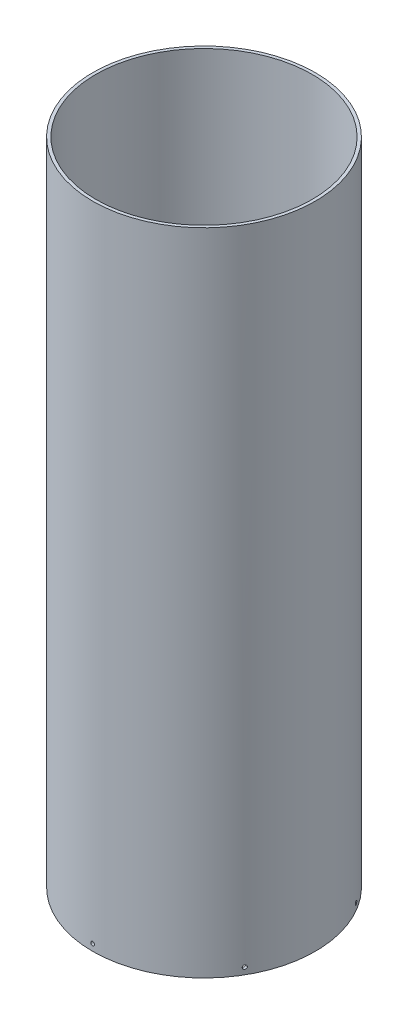
SolidWorks part; units mm, degrees
ref_plane "Front Plane" through (0, 0, 0) normal (0, 0, 1) x (1, 0, 0)
ref_plane "Top Plane" through (0, 0, 0) normal (0, 1, 0) x (1, 0, 0)
ref_plane "Right Plane" through (0, 0, 0) normal (1, 0, 0) x (0, 0, -1)
sketch "Sketch1" plane through (0, 0, 0) normal (0, 1, 0) x (1, 0, 0)
  circle A0 centre (0, 0) radius 76.2
  circle A1 centre (0, 0) radius 78.359
  dimension "D1" = 152.4
  dimension "D2" = 156.718
extrude "Boss-Extrude1" add sketch "Sketch1" along normal blind 457.2
ref_axis "Axis1" through (0, 457.2, 0) along (0, -1, 0)
sketch "Sketch2" plane through (0, 0, 0) normal (0, 0, 1) x (1, 0, 0)
  line L0 (0, 0) -> (0, 4.7625) construction
  circle A0 centre (0, 4.7625) radius 1.3526
  dimension "D1" = 2.7051
  dimension "D2" = 4.7625
extrude "Cut-Extrude1" cut sketch "Sketch2" against normal through all
pattern_circular "CirPattern1" count 6 over 360 about axis through (0, 457.2, 0) along (0, -1, 0) of "Cut-Extrude1"
equation "\"D1@Boss-Extrude1\"=\"Aft_Upper_Length\""
equation "\"AB_Coupling_Section_Length\"= 0.375in"
equation "\"AB_Coupler_Num_Screws\"= 6"
equation "\"AB_Coupling_Screw_Diameter\"= 0.1065in"
equation "\"AB_Coupler_OD_Length\"= 2in"
equation "\"AB_Coupler_Length\"= \"AB_Coupler_OD_Length\" + \"AB_Coupling_Section_Length\" * 2"
equation "\"D1@Sketch2\"=\"AB_Coupling_Screw_Diameter\""
equation "\"D2@Sketch2\"=\"AB_Coupling_Section_Length\"/2"
equation "\"D1@CirPattern1\"=\"AB_Coupler_Num_Screws\""
equation "\"Aft_Section_Length\"= 40in"
equation "\"Aft_Upper_Length\"= \"Aft_Section_Length\" - \"Aft_Lower_Length\" - \"AB_Coupler_OD_Length\""
equation "\"Aft_Lower_Length\"= 20in"
